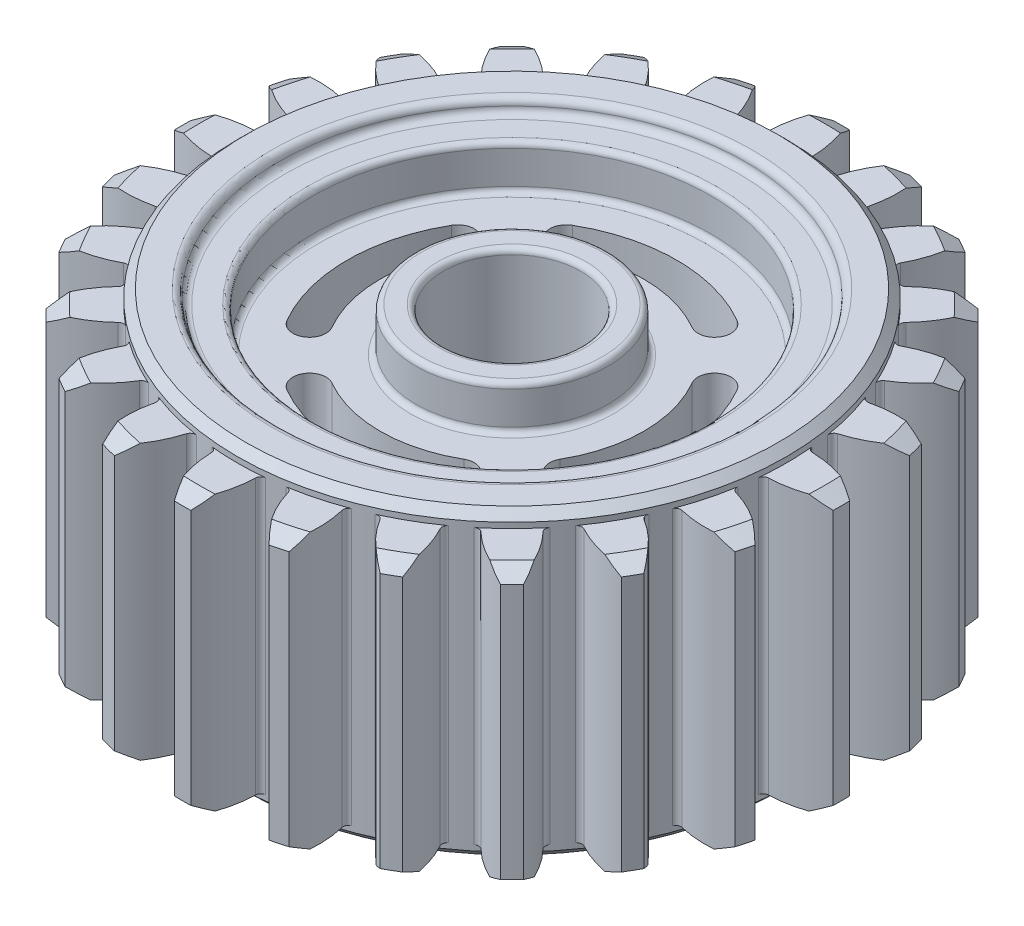
SolidWorks part; units mm, degrees
note: The reader was unsure of these and kept them because the rebuilt part matched: shared geometry of "Sketch1<3>", "Sketch1<4>".
ref_plane "Front Plane" through (0, 0, 0) normal (0, 0, 1) x (1, 0, 0)
ref_plane "Top Plane" through (0, 0, 0) normal (0, 1, 0) x (1, 0, 0)
ref_plane "Right Plane" through (0, 0, 0) normal (1, 0, 0) x (0, 0, -1)
sketch "Sketch1" plane through (0, 0, 0) normal (0, 1, 0) x (1, 0, 0)
  line L0 (0, 0) -> (0, -50000) construction
  line L1 (0, 0) -> (50000, 0) construction
  circle A0 centre (0, 0) radius 50
  circle A1 centre (0, 0) radius 60
  arc A2 (4, 49.8397) -> (1.5, 59.9812) centre (-15.9949, 50.2896) ccw
  arc A3 (-4, 49.8397) -> (-1.5, 59.9812) centre (15.9949, 50.2896) cw
  arc A4 (16.7632, 47.1062) -> (16.9732, 57.5492) centre (-2.434, 52.7159) ccw
  arc A5 (9.0358, 49.1768) -> (14.0754, 58.3257) centre (28.4658, 44.4363) cw
  arc A6 (28.384, 41.1625) -> (31.2897, 51.1953) centre (11.2928, 51.5496) ccw
  arc A7 (21.4558, 45.1625) -> (28.6916, 52.6953) centre (38.9968, 35.5546) cw
  arc A8 (38.0704, 32.4136) -> (43.4738, 41.3525) centre (24.25, 46.8703) ccw
  arc A9 (32.4136, 38.0704) -> (41.3525, 43.4738) centre (46.8703, 24.25) cw
  arc A10 (45.1625, 21.4558) -> (52.6953, 28.6916) centre (35.5546, 38.9968) ccw
  arc A11 (41.1625, 28.384) -> (51.1953, 31.2897) centre (51.5496, 11.2928) cw
  arc A12 (49.1768, 9.0358) -> (58.3257, 14.0754) centre (44.4363, 28.4658) ccw
  arc A13 (47.1062, 16.7632) -> (57.5492, 16.9732) centre (52.7159, -2.434) cw
  arc A14 (49.8397, -4) -> (59.9812, -1.5) centre (50.2896, 15.9949) ccw
  arc A15 (49.8397, 4) -> (59.9812, 1.5) centre (50.2896, -15.9949) cw
  arc A16 (47.1062, -16.7632) -> (57.5492, -16.9732) centre (52.7159, 2.434) ccw
  arc A17 (49.1768, -9.0358) -> (58.3257, -14.0754) centre (44.4363, -28.4658) cw
  arc A18 (41.1625, -28.384) -> (51.1953, -31.2897) centre (51.5496, -11.2928) ccw
  arc A19 (45.1625, -21.4558) -> (52.6953, -28.6916) centre (35.5546, -38.9968) cw
  arc A20 (32.4136, -38.0704) -> (41.3525, -43.4738) centre (46.8703, -24.25) ccw
  arc A21 (38.0704, -32.4136) -> (43.4738, -41.3525) centre (24.25, -46.8703) cw
  arc A22 (21.4558, -45.1625) -> (28.6916, -52.6953) centre (38.9968, -35.5546) ccw
  arc A23 (28.384, -41.1625) -> (31.2897, -51.1953) centre (11.2928, -51.5496) cw
  arc A24 (9.0358, -49.1768) -> (14.0754, -58.3257) centre (28.4658, -44.4363) ccw
  arc A25 (16.7632, -47.1062) -> (16.9732, -57.5492) centre (-2.434, -52.7159) cw
  arc A26 (-4, -49.8397) -> (-1.5, -59.9812) centre (15.9949, -50.2896) ccw
  arc A27 (4, -49.8397) -> (1.5, -59.9812) centre (-15.9949, -50.2896) cw
  arc A28 (-16.7632, -47.1062) -> (-16.9732, -57.5492) centre (2.434, -52.7159) ccw
  arc A29 (-9.0358, -49.1768) -> (-14.0754, -58.3257) centre (-28.4658, -44.4363) cw
  arc A30 (-28.384, -41.1625) -> (-31.2897, -51.1953) centre (-11.2928, -51.5496) ccw
  arc A31 (-21.4558, -45.1625) -> (-28.6916, -52.6953) centre (-38.9968, -35.5546) cw
  arc A32 (-38.0704, -32.4136) -> (-43.4738, -41.3525) centre (-24.25, -46.8703) ccw
  arc A33 (-32.4136, -38.0704) -> (-41.3525, -43.4738) centre (-46.8703, -24.25) cw
  arc A34 (-45.1625, -21.4558) -> (-52.6953, -28.6916) centre (-35.5546, -38.9968) ccw
  arc A35 (-41.1625, -28.384) -> (-51.1953, -31.2897) centre (-51.5496, -11.2928) cw
  arc A36 (-49.1768, -9.0358) -> (-58.3257, -14.0754) centre (-44.4363, -28.4658) ccw
  arc A37 (-47.1062, -16.7632) -> (-57.5492, -16.9732) centre (-52.7159, 2.434) cw
  arc A38 (-49.8397, 4) -> (-59.9812, 1.5) centre (-50.2896, -15.9949) ccw
  arc A39 (-49.8397, -4) -> (-59.9812, -1.5) centre (-50.2896, 15.9949) cw
  arc A40 (-47.1062, 16.7632) -> (-57.5492, 16.9732) centre (-52.7159, -2.434) ccw
  arc A41 (-49.1768, 9.0358) -> (-58.3257, 14.0754) centre (-44.4363, 28.4658) cw
  arc A42 (-41.1625, 28.384) -> (-51.1953, 31.2897) centre (-51.5496, 11.2928) ccw
  arc A43 (-45.1625, 21.4558) -> (-52.6953, 28.6916) centre (-35.5546, 38.9968) cw
  arc A44 (-32.4136, 38.0704) -> (-41.3525, 43.4738) centre (-46.8703, 24.25) ccw
  arc A45 (-38.0704, 32.4136) -> (-43.4738, 41.3525) centre (-24.25, 46.8703) cw
  arc A46 (-21.4558, 45.1625) -> (-28.6916, 52.6953) centre (-38.9968, 35.5546) ccw
  arc A47 (-28.384, 41.1625) -> (-31.2897, 51.1953) centre (-11.2928, 51.5496) cw
  arc A48 (-9.0358, 49.1768) -> (-14.0754, 58.3257) centre (-28.4658, 44.4363) ccw
  arc A49 (-16.7632, 47.1062) -> (-16.9732, 57.5492) centre (2.434, 52.7159) cw
  circle A50 centre (0, 0) radius 12.5
  circle A51 centre (0, 0) radius 42.5
  dimension "D1" = 120
  dimension "D2" = 100
  dimension "D5" = 20
  dimension "D7" = 25
  dimension "D9" = 85
  dimension "D3" = 3
  dimension "D4" = 8
  dimension "D6" = 24
extrude "Boss-Extrude1" add sketch "Sketch1" along normal mid plane 50
extrude "Boss-Extrude2" add sketch "Sketch1<3>" along normal mid plane 55 contours A0 A51
sketch "Sketch1<3>" plane through (0, 0, 0) normal (0, 1, 0) x (1, 0, 0) same geometry as "Sketch1"
extrude "Boss-Extrude3" add sketch "Sketch1<4>" along normal mid plane 50 contours A11 A0 A10 A1 | A13 A0 A12 A1 | A15 A0 A14 A1 | A17 A0 A16 A1 | A19 A0 A18 A1 | A21 A0 A20 A1 | A23 A0 A22 A1 | A25 A0 A24 A1 | A27 A0 A26 A1 | A29 A0 A28 A1 | A31 A0 A30 A1 | A33 A0 A32 A1 | A35 A0 A34 A1 | A37 A0 A36 A1 | A39 A0 A38 A1 | A41 A0 A40 A1 | A43 A0 A42 A1 | A45 A0 A44 A1 | A47 A0 A46 A1 | A49 A0 A48 A1 | A3 A0 A2 A1 | A7 A0 A6 A1 | A9 A0 A8 A1 | A5 A0 A4 A1
sketch "Sketch1<4>" plane through (0, 0, 0) normal (0, 1, 0) x (1, 0, 0) same geometry as "Sketch1"
fillet "Fillet1" radius 1.25 4 edges at (0, 27.5, 42.5) (0, 25, 42.5) (0, -25, 42.5) (0, -27.5, 42.5)
chamfer "Chamfer1" distance 1.5 angle 45 2 edges at (0, -27.5, 50) (0, 27.5, 50)
sketch "Sketch2" plane through (0, 0, 0) normal (0, 0, 1) x (1, 0, 0)
  line L0 (0, 0) -> (0, -50000) construction
  line L1 (61.3226, 25) -> (57, 25)
  line L2 (57.5492, 25) -> (47.1062, 25) construction
  line L3 (57, 25) -> (61.3226, 22.5043)
  line L5 (61.3226, 22.5043) -> (61.3226, 25)
  dimension "D1" = 30
  dimension "D2" = 114
revolve "Cut-Revolve1" cut sketch "Sketch2" angle 360 about L0
mirror "Mirror1" about plane through (0, 0, 0) normal (0, 1, 0) of "Cut-Revolve1"
fillet "Fillet2" radius 1 48 edges at (-49.8397, 0, -4) (-49.8397, 0, 4) (-16.7632, 0, 47.1062) (-9.0358, 0, 49.1768) (-4, 0, 49.8397) (4, 0, 49.8397) (9.0358, 0, 49.1768) (16.7632, 0, 47.1062) (21.4558, 0, 45.1625) (28.384, 0, 41.1625) (32.4136, 0, 38.0704) (38.0704, 0, 32.4136) (45.1625, 0, 21.4558) (41.1625, 0, 28.384) (47.1062, 0, 16.7632) (49.1768, 0, 9.0358) (49.8397, 0, 4) (49.8397, 0, -4) (49.1768, 0, -9.0358) (47.1062, 0, -16.7632) (45.1625, 0, -21.4558) (41.1625, 0, -28.384) (38.0704, 0, -32.4136) (32.4136, 0, -38.0704) (28.384, 0, -41.1625) (21.4558, 0, -45.1625) (16.7632, 0, -47.1062) (9.0358, 0, -49.1768) (4, 0, -49.8397) (-9.0358, 0, -49.1768) (-21.4558, 0, -45.1625) (-32.4136, 0, -38.0704) (-4, 0, -49.8397) (-16.7632, 0, -47.1062) (-28.384, 0, -41.1625) (-38.0704, 0, -32.4136) (-45.1625, 0, -21.4558) (-41.1625, 0, -28.384) (-21.4558, 0, 45.1625) (-28.384, 0, 41.1625) (-38.0704, 0, 32.4136) (-32.4136, 0, 38.0704) (-41.1625, 0, 28.384) (-45.1625, 0, 21.4558) (-47.1062, 0, 16.7632) (-49.1768, 0, -9.0358) (-47.1062, 0, -16.7632) (-49.1768, 0, 9.0358)
sketch "Sketch3" plane through (0, 25, 0) normal (0, 1, 0) x (1, 0, 0)
  circle A0 centre (0, 0) radius 12.5 construction
  circle A1 centre (0, 0) radius 41.25 construction
  circle A2 centre (0, 0) radius 12.5
  circle A3 centre (0, 0) radius 41.25
  circle A4 centre (0, 0) radius 36.25
  circle A5 centre (0, 0) radius 17.5
  dimension "D1" = 5
  dimension "D2" = 5
extrude "Cut-Extrude1" cut sketch "Sketch3" against normal blind 8 contours A4 A5
mirror "Mirror2" about plane through (0, 0, 0) normal (0, 1, 0) of "Cut-Extrude1"
sketch "Sketch4" plane through (0, 17, 0) normal (0, 1, 0) x (1, 0, 0)
  line L0 (0, 0) -> (50000, 0) construction
  arc A0 (23.3827, -13.5) -> (23.3827, 13.5) centre (0, 0) ccw construction
  arc A1 (25.9808, -15) -> (25.9808, 15) centre (0, 0) ccw
  arc A2 (20.7846, -12) -> (20.7846, 12) centre (0, 0) ccw
  arc A3 (20.7846, -12) -> (25.9808, -15) centre (23.3827, -13.5) ccw
  arc A4 (25.9808, 15) -> (20.7846, 12) centre (23.3827, 13.5) ccw
  arc A5 (-13.5, -23.3827) -> (13.5, -23.3827) centre (0, 0) ccw construction
  arc A6 (-15, -25.9808) -> (15, -25.9808) centre (0, 0) ccw
  arc A7 (-12, -20.7846) -> (12, -20.7846) centre (0, 0) ccw
  arc A8 (-12, -20.7846) -> (-15, -25.9808) centre (-13.5, -23.3827) ccw
  arc A9 (15, -25.9808) -> (12, -20.7846) centre (13.5, -23.3827) ccw
  arc A10 (-23.3827, 13.5) -> (-23.3827, -13.5) centre (0, 0) ccw construction
  arc A11 (-25.9808, 15) -> (-25.9808, -15) centre (0, 0) ccw
  arc A12 (-20.7846, 12) -> (-20.7846, -12) centre (0, 0) ccw
  arc A13 (-20.7846, 12) -> (-25.9808, 15) centre (-23.3827, 13.5) ccw
  arc A14 (-25.9808, -15) -> (-20.7846, -12) centre (-23.3827, -13.5) ccw
  arc A15 (13.5, 23.3827) -> (-13.5, 23.3827) centre (0, 0) ccw construction
  arc A16 (15, 25.9808) -> (-15, 25.9808) centre (0, 0) ccw
  arc A17 (12, 20.7846) -> (-12, 20.7846) centre (0, 0) ccw
  arc A18 (12, 20.7846) -> (15, 25.9808) centre (13.5, 23.3827) ccw
  arc A19 (-15, 25.9808) -> (-12, 20.7846) centre (-13.5, 23.3827) ccw
  point P4 (27, 0)
  point P17 (0, -27)
  point P24 (-27, 0)
  point P31 (0, 27)
  dimension "D1" = 27
  dimension "D2" = 3
  dimension "D3" = 60
  dimension "D4" = 4
extrude "Cut-Extrude2" cut sketch "Sketch4" against normal up to next
fillet "Fillet3" radius 1 9 edges at (0, 25, 17.5) (0, 25, 12.5) (0, 17, 17.5) (0, 17, 36.25) (0, 25, 36.25) (0, -25, 36.25) (0, -25, 17.5) (0, -17, 17.5) (0, -17, 36.25)
